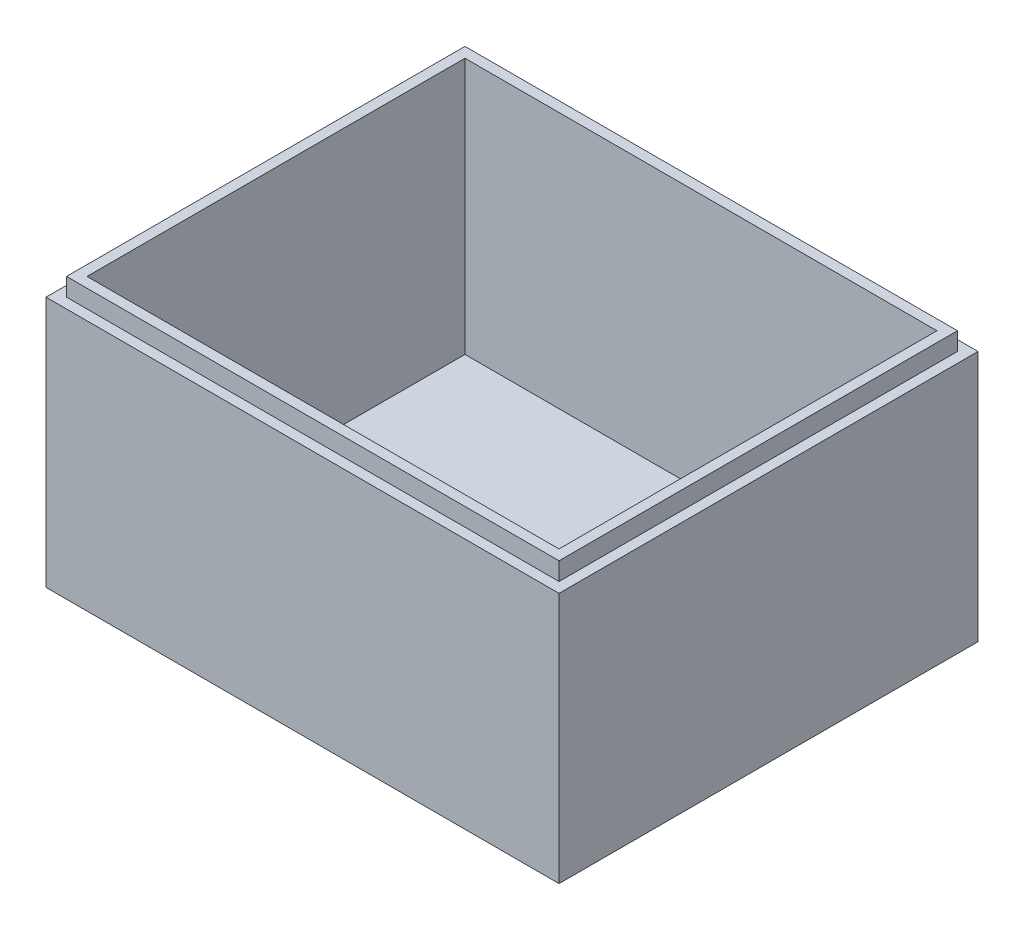
SolidWorks part; units mm, degrees
ref_plane "Front Plane" through (0, 0, 0) normal (0, 0, 1) x (1, 0, 0)
ref_plane "Top Plane" through (0, 0, 0) normal (0, 1, 0) x (1, 0, 0)
ref_plane "Right Plane" through (0, 0, 0) normal (1, 0, 0) x (0, 0, -1)
sketch "BatteryAndOuterWalls" plane through (0, 0, 0) normal (0, 1, 0) x (1, 0, 0)
  line L0 (30, -24.5) -> (30, 24.5)
  line L1 (27.6, -22.1) -> (-27.6, -22.1)
  line L2 (27.6, -22.1) -> (27.6, 22.1)
  line L3 (27.6, 22.1) -> (-27.6, 22.1)
  line L4 (-27.6, -22.1) -> (-27.6, 22.1)
  line L5 (27.6, -22.1) -> (-27.6, 22.1) construction
  line L6 (27.6, 22.1) -> (-27.6, -22.1) construction
  line L7 (30, 24.5) -> (-30, 24.5)
  line L8 (-30, -24.5) -> (-30, 24.5)
  line L9 (30, -24.5) -> (-30, -24.5)
  point P0 (0, 0)
  dimension "D1" = 55.2
  dimension "D2" = 44.2
  dimension "D4" = 60
  dimension "D5" = 49
  dimension "D3" = 2.4
extrude "Walls" add sketch "BatteryAndOuterWalls" along normal blind 30
sketch "SinkRim" plane through (0, 30, 0) normal (0, 1, 0) x (1, 0, 0)
  line L0 (-28.8, 23.3) -> (-28.8, -23.3)
  line L5 (-27.6, 22.1) -> (27.6, 22.1)
  line L6 (-27.6, 22.1) -> (-27.6, -22.1)
  line L7 (-27.6, -22.1) -> (27.6, -22.1)
  line L8 (27.6, 22.1) -> (27.6, -22.1)
  line L9 (-28.8, -23.3) -> (28.8, -23.3)
  line L10 (28.8, 23.3) -> (28.8, -23.3)
  line L11 (-28.8, 23.3) -> (28.8, 23.3)
  line L12 (-30, 24.5) -> (30, 24.5)
  line L13 (30, 24.5) -> (30, -24.5)
  line L14 (-30, -24.5) -> (30, -24.5)
  line L15 (-30, 24.5) -> (-30, -24.5)
  line M5 (-30, -24.5) -> (30, -24.5)
  line M6 (30, -24.5) -> (30, 24.5)
  line M7 (30, 24.5) -> (-30, 24.5)
  line M8 (-30, 24.5) -> (-30, -24.5)
  dimension "D1" = 1.2
  dimension "D2" = 1.2
sketch "Sketch2" plane through (0, 0, 0) normal (0, -1, 0) x (1, 0, 0)
  line L0 (-30, 24.5) -> (30, 24.5) construction
  line L5 (-30, 24.5) -> (30, 24.5)
  line L6 (-30, 24.5) -> (-30, -24.5)
  line L7 (-30, -24.5) -> (30, -24.5)
  line L8 (30, 24.5) -> (30, -24.5)
  line L9 (-30, -24.5) -> (-30, 24.5) construction
extrude "Bottom" add sketch "Sketch2" along normal blind 1.5
extrude "Top-Cut" cut sketch "SinkRim" against normal blind 2.1 contours L0 L11 L10 L9 M8 M5 M6 M7 region at (0, 30, -23.7253)
sketch "FrontRail" plane through (30, 0, 0) normal (1, 0, 0) x (0, 0, -1)
  line L0 (-24.5, 27.9) -> (-24.5, -1.5) construction
  line L1 (-22.1, 30) -> (22.1, 30)
  line L2 (-22.1, 30) -> (-22.1, 0)
  line L3 (-22.1, 0) -> (22.1, 0)
  line L4 (22.1, 30) -> (22.1, 0)
  line L5 (24.5, -1.5) -> (-24.5, -1.5) construction
  line L6 (24.5, 27.9) -> (24.5, -1.5) construction
  line L7 (23.3, 30) -> (-23.3, 30) construction
  line L8 (-22.1, 13) -> (-22.1, 14)
  line L9 (-22.1, 15) -> (-19.1, 15)
  line L10 (-22.1, 15) -> (-22.1, 14)
  line L11 (-22.1, 14) -> (-19.5, 14)
  line L12 (-19.1, 15) -> (-19.1, 14.4)
  line L29 (-22.1, 13) -> (-22.1, 14)
  line L30 (-22.1, 14) -> (-22.1, 13)
  arc A0 (-19.5, 14) -> (-22.1, 13) centre (-19.5, 10.12) ccw
  arc A1 (-19.1, 14.4) -> (-19.5, 14) centre (-19.5, 14.4) cw
  point P21 (0, 0)
  point P22 (-19.1, 14)
  point P23 (0, 0)
  point P24 (0, 0)
  point P25 (0, 0)
  point P26 (-19.1, 14)
  point P27 (0, 0)
  point P28 (0, 0)
  point P29 (-19.5, 13.9596)
  dimension "D1" = 2.4
  dimension "D2" = 1.5
  dimension "D3" = 2.4
  dimension "D4" = 0
  dimension "D5" = 14
  dimension "D7" = 3
  dimension "D8" = 1
  dimension "D9" = 15
extrude "Boss-Extrude2" add sketch "FrontRail" against normal blind 60 contours A0 L11 L2 | A1 L12 L9 L2 L11 region at (30, 14.5048, 20.6163) region at (30, 13.708, 21.4679)
